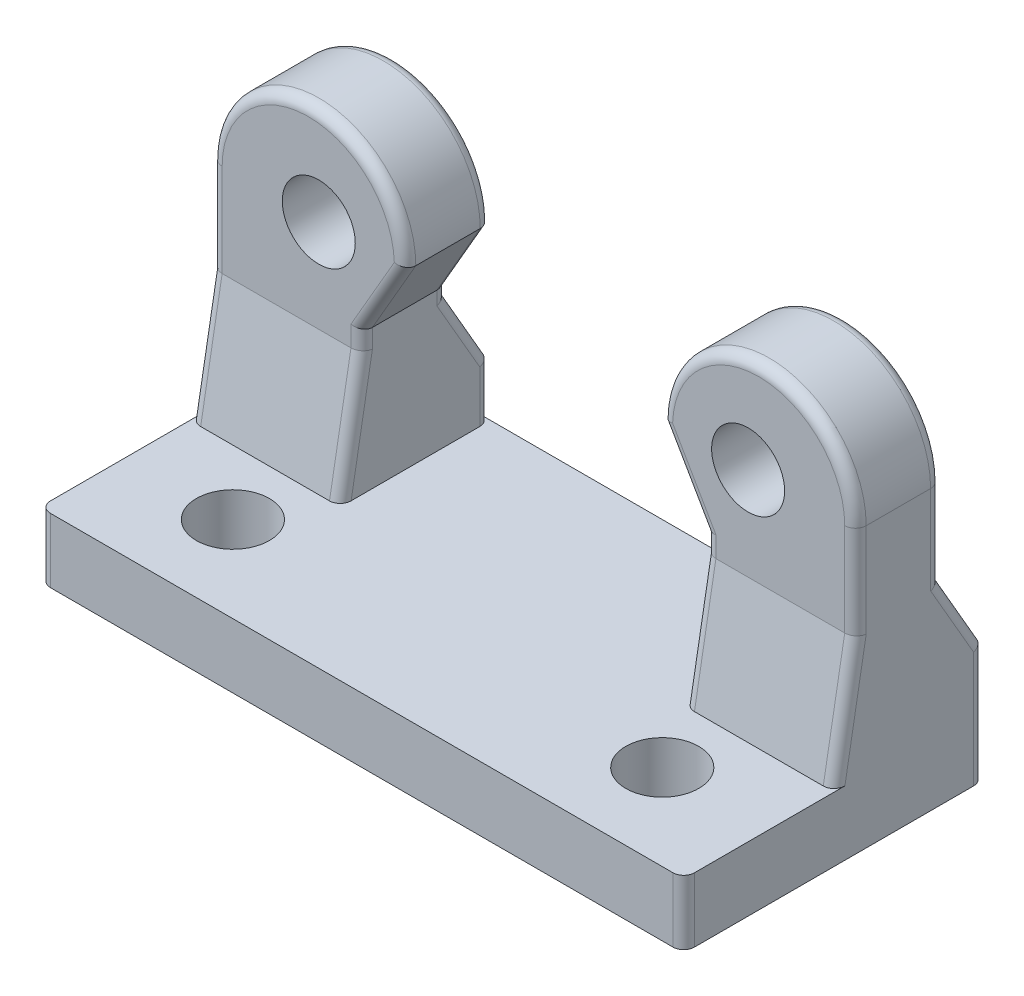
SolidWorks part; units mm, degrees
ref_plane "Front Plane" through (0, 0, 0) normal (0, 0, 1) x (1, 0, 0)
ref_plane "Top Plane" through (0, 0, 0) normal (0, 1, 0) x (1, 0, 0)
ref_plane "Right Plane" through (0, 0, 0) normal (1, 0, 0) x (0, 0, -1)
sketch "Sketch1" plane through (0, 0, 0) normal (0, 0, 1) x (1, 0, 0)
  line L0 (-10, 10) -> (10, 10) construction
  line L1 (-15, -3) -> (15, -3)
  line L2 (-15, -3) -> (-15, 10)
  line L3 (-15, 10) -> (-10, 10) construction
  line L4 (15, -3) -> (15, 10)
  line L5 (0, 10) -> (0, 0) construction
  line L6 (-8, 6.5) -> (8, 6.5) construction
  line L7 (10, 10) -> (15, 10) construction
  line L8 (-8, 6.5) -> (-5.9793, 10)
  line L9 (8, 6.5) -> (5.9793, 10)
  line L23 (-8, 6.5) -> (-8, 0)
  line L30 (-8, 0) -> (8, 0)
  line L31 (8, 0) -> (8, 6.5)
  arc A0 (-15, 10) -> (-5.9793, 10) centre (-10.4896, 10) cw
  arc A1 (15, 10) -> (5.9793, 10) centre (10.4896, 10) ccw
  circle A2 centre (-10, 10) radius 1.7
  circle A3 centre (10, 10) radius 1.7
  point P0 (0, 0)
  point P14 (-10, 10)
  point P15 (10, 10)
  point P26 (0, 0)
  dimension "D1" = 3.4
  dimension "D2" = 3
  dimension "D3" = 30
  dimension "D4" = 16
  dimension "D5" = 60
  dimension "D6" = 20
  dimension "D7" = 60
  dimension "D8" = 10
  dimension "D9" = 3.5
extrude "Boss-Extrude1" add sketch "Sketch1" along normal blind 4
sketch "Sketch2" plane through (0, 0, 4) normal (0, 0, 1) x (1, 0, 0)
  line L0 (15, -3) -> (15, 10) construction
  line L1 (-15, -3) -> (15, -3)
  line L2 (-15, -3) -> (-15, 0)
  line L3 (-15, 0) -> (15, 0)
  line L4 (15, -3) -> (15, 0)
extrude "Boss-Extrude2" add sketch "Sketch2" along normal blind 8 and the other way blind 6
sketch "Sketch3" plane through (0, 0, 0) normal (0, 1, 0) x (1, 0, 0)
  line L0 (-15, -8) -> (15, -8) construction
  line L2 (-15, -12) -> (-15, -4) construction
  line L3 (15, -12) -> (15, -4) construction
  line L4 (-10, -8) -> (10, -8) construction
  circle A0 centre (-10, -8) radius 1.7
  circle A1 centre (10, -8) radius 1.7
  point P14 (0, -8)
  dimension "D2" = 3.4
  dimension "D1" = 20
extrude "Cut-Extrude1" cut sketch "Sketch3" against normal through all
chamfer "Chamfer2" distance 6 angle 30 2 edges at (-11.5, 0, 0) (11.5, 0, 0) first distance on face at (-10.3959, 6.2021, 0) first distance on face at (10.3959, 6.2021, 0)
chamfer "Chamfer3" distance 1 angle 80 2 edges at (11.5, 0, 4) (-11.5, 0, 4) first distance on face at (10, 0, 9.7)
fillet "Fillet1" radius 0.5 30 edges at (-10.4896, 14.5104, 0) (10.4896, 14.5104, 0) (10.4896, 14.5104, 4) (-10.4896, 14.5104, 4) (6.9896, 8.25, 0) (6.9896, 8.25, 4) (-6.9896, 8.25, 0) (-6.9896, 8.25, 4) (-15, 8, 0) (15, 8, 0) (-15, 4.2679, -1) (-8, 4.2679, -1) (8, 4.2679, -1) (15, 4.2679, -1) (15, 7.8356, 4) (8, 6.0856, 4) (-8, 6.0856, 4) (-15, -1.5, 12) (-15, 7.8356, 4) (-15, -0.2321, -2) (-8, 1.2679, -2) (8, 1.2679, -2) (15, -0.2321, -2) (15, -1.5, 12) (8, 6.25, 0) (-8, 6.25, 0) (-15, 2.8356, 4.5) (-8, 2.8356, 4.5) (8, 2.8356, 4.5) (15, 2.8356, 4.5)
